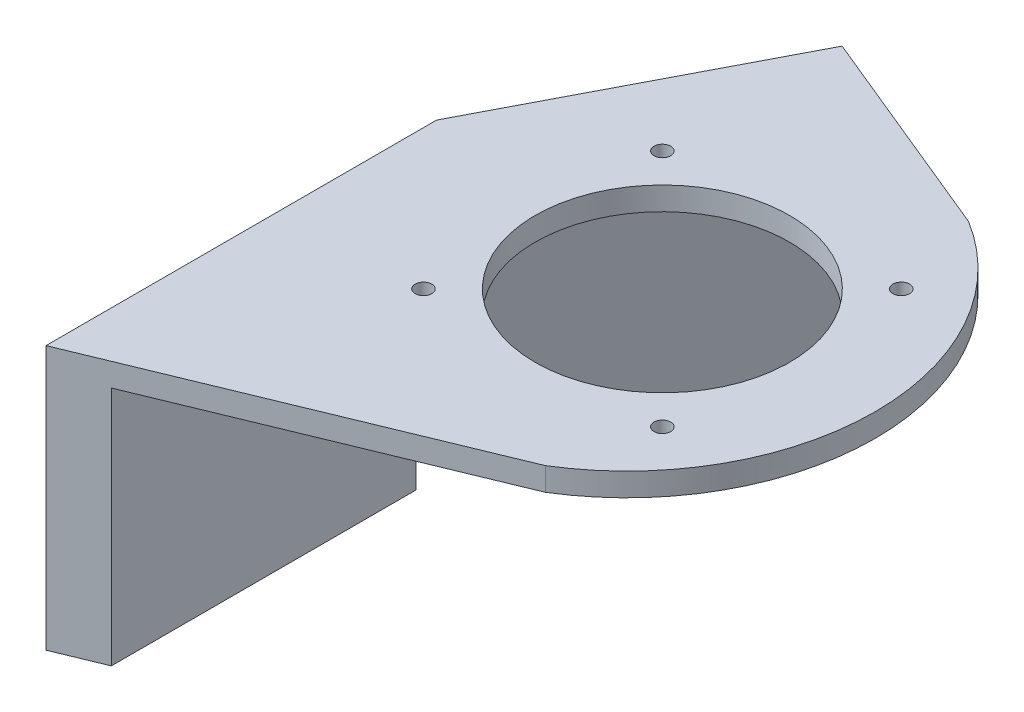
SolidWorks part; units mm, degrees
ref_plane "Front Plane" through (0, 0, 0) normal (0, 0, 1) x (1, 0, 0)
ref_plane "Top Plane" through (0, 0, 0) normal (0, 1, 0) x (1, 0, 0)
ref_plane "Right Plane" through (0, 0, 0) normal (1, 0, 0) x (0, 0, -1)
sketch "Sketch2" plane through (0, 0, 0) normal (0, 1, 0) x (1, 0, 0)
  line L10 (109.5, -38.6) -> (155.4807, -38.6) construction
  line L16 (104.5, -77.2) -> (142.7026, -61.4563)
  line L23 (109.5, -35) -> (123.6013, -7.8719) construction
  line L26 (104.5, 0) -> (104.5, -77.2) construction
  line L27 (109.5, -35) -> (104.5, -35) construction
  line L29 (104.5, -42.2) -> (109.5, -42.2) construction
  line L30 (109.5, -42.2) -> (109.5, -75.1394) construction
  line L31 (116.4903, -54.6) -> (148.4903, -22.6) construction
  line L36 (116.4903, -22.6) -> (148.4903, -54.6) construction
  line L37 (104.5, -35) -> (119.4834, -6.1748) construction
  line L38 (104.5, -35) -> (119.4834, -6.1748)
  line L39 (142.7026, -15.7437) -> (119.4834, -6.1748)
  line L40 (104.5, -35) -> (104.5, -77.2)
  arc A2 (142.7026, -15.7437) -> (142.7026, -61.4563) centre (128.65, -38.6) cw
  circle A3 centre (132.4903, -38.6) radius 13.75
  circle A4 centre (145.395, -25.6953) radius 0.9
  circle A5 centre (119.5856, -51.5047) radius 0.9
  circle A6 centre (119.5856, -25.6953) radius 0.9
  circle A7 centre (145.395, -51.5047) radius 0.9
  dimension "D3" = 35
  dimension "D5" = 32
  dimension "D9" = 18.25
  dimension "D1" = 35
  dimension "D2" = 5
  dimension "D4" = 5
  dimension "D6" = 32
extrude "Boss-Extrude1" add sketch "Sketch2" along normal blind 2.5
sketch "Sketch3" plane through (0, 0, 0) normal (0, -1, 0) x (1, 0, 0)
  line L11 (104.5, 42.2) -> (109.5, 42.2)
  line L12 (109.5, 42.2) -> (109.5, 75.1394)
  line L13 (109.5, 75.1394) -> (104.5, 77.2)
  line L14 (104.5, 77.2) -> (104.5, 42.2)
  line L15 (109.5, 35) -> (104.5, 35)
  line L16 (104.5, 35) -> (119.4834, 6.1748)
  line L17 (119.4834, 6.1748) -> (123.6013, 7.8719)
  line L18 (123.6013, 7.8719) -> (109.5, 35)
extrude "Boss-Extrude2" add sketch "Sketch3" along normal blind 26
sketch "Sketch5" plane through (104.5, 0, 0) normal (-1, 0, 0) x (0, 0, 1)
  line L0 (42.2, -26) -> (42.2, 0) construction
  line L1 (35, 0) -> (42.2, 0)
  line L2 (35, 0) -> (35, -21)
  line L3 (35, -21) -> (42.2, -21)
  line L4 (42.2, 0) -> (42.2, -21)
  line L5 (77.2, -26) -> (42.2, -26) construction
  dimension "D1" = 5
extrude "Boss-Extrude5" add sketch "Sketch5" against normal blind 5
